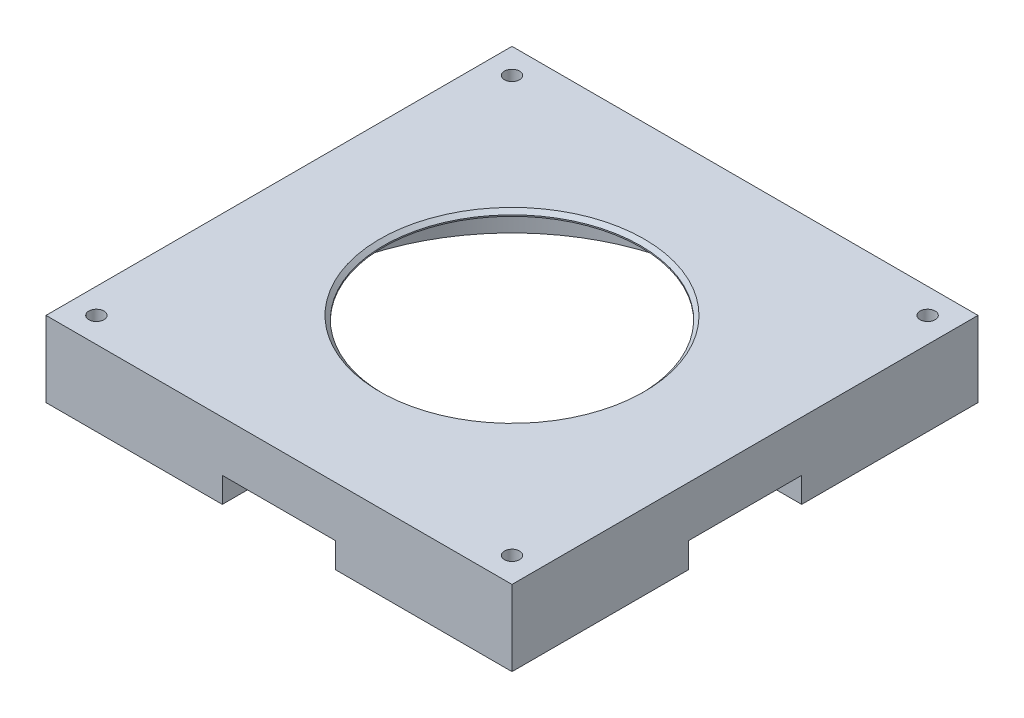
SolidWorks part; units mm, degrees
material "PBT General Purpose"
ref_plane "Front Plane" through (0, 0, 0) normal (0, 0, 1) x (1, 0, 0)
ref_plane "Top Plane" through (0, 0, 0) normal (0, 1, 0) x (1, 0, 0)
ref_plane "Right Plane" through (0, 0, 0) normal (1, 0, 0) x (0, 0, -1)
sketch "Sketch1" plane through (0, 0, 0) normal (0, 0, 1) x (1, 0, 0)
  line L1 (51, -2) -> (82.5, -2)
  line L2 (82.5, -2) -> (82.5, -30)
  line L5 (82.5, -30) -> (85.5, -30)
  line L6 (85.5, -30) -> (85.5, 0)
  line L7 (85.5, 0) -> (51, 0)
  line L8 (51, -2) -> (51, 0)
  line L9 (0, 0) -> (51, 0) construction
  line L10 (0, 0) -> (0, -6.871) construction
  dimension "D1" = 3
  dimension "D3" = 2
  dimension "D5" = 30
  dimension "D6" = 82.5
  dimension "D7" = 51
revolve "Revolve1" add sketch "Sketch1" angle 360 about L10
chamfer "Chamfer1" distance 1.5 angle 45 1 edges at (0, 0, 51)
sketch "Sketch2" plane through (0, -30, 0) normal (0, -1, 0) x (1, 0, 0)
  line L1 (-92.5, -92.5) -> (92.5, -92.5)
  line L2 (-92.5, -92.5) -> (-92.5, 92.5)
  line L3 (-92.5, 92.5) -> (92.5, 92.5)
  line L4 (92.5, -92.5) -> (92.5, 92.5)
  line L5 (-92.5, -92.5) -> (92.5, 92.5) construction
  line L6 (-92.5, 92.5) -> (92.5, -92.5) construction
  line L7 (-82.5, -82.5) -> (82.5, -82.5) construction
  line L8 (-82.5, -82.5) -> (-82.5, 82.5) construction
  line L9 (-82.5, 82.5) -> (82.5, 82.5) construction
  line L10 (82.5, -82.5) -> (82.5, 82.5) construction
  line L11 (-82.5, -82.5) -> (82.5, 82.5) construction
  line L12 (-82.5, 82.5) -> (82.5, -82.5) construction
  circle A0 centre (0, 0) radius 85.5
  circle A1 centre (0, 0) radius 85.5 construction
  circle A6 centre (-82.5, -82.5) radius 3
  circle A7 centre (82.5, -82.5) radius 3
  circle A8 centre (82.5, 82.5) radius 3
  circle A9 centre (-82.5, 82.5) radius 3
  dimension "D3" = 6
  dimension "D1" = 185
  dimension "D2" = 165
extrude "Boss-Extrude1" add sketch "Sketch2" against normal up to surface (30 mm away) up to face at (0, 0, -52.5)
sketch "Sketch3" plane through (-92.5, 0, 0) normal (-1, 0, 0) x (0, 0, 1)
  line L0 (92.5, -30) -> (-92.5, -30) construction
  line L1 (-22.5, -30) -> (22.5, -30)
  line L2 (-22.5, -30) -> (-22.5, -20)
  line L3 (-22.5, -20) -> (22.5, -20)
  line L4 (22.5, -30) -> (22.5, -20)
  line L5 (0, 0) -> (0, -20) construction
  line L6 (92.5, 0) -> (92.5, -30) construction
  dimension "D1" = 10
  dimension "D2" = 70
extrude "Cut-Extrude1" cut sketch "Sketch3" against normal through all
sketch "Sketch4" plane through (0, 0, -92.5) normal (0, 0, -1) x (-1, 0, 0)
  line L0 (92.5, -30) -> (-92.5, -30) construction
  line L1 (-22.5, -30) -> (22.5, -30)
  line L2 (-22.5, -30) -> (-22.5, -20)
  line L3 (-22.5, -20) -> (22.5, -20)
  line L4 (22.5, -30) -> (22.5, -20)
  line L5 (0, 0) -> (0, -20) construction
  line L6 (92.5, 0) -> (92.5, -30) construction
  dimension "D1" = 10
  dimension "D2" = 70
extrude "Cut-Extrude2" cut sketch "Sketch4" against normal through all
sketch3d "3DSketch2"
  point P0 (-94.5, 0, 94.5)
